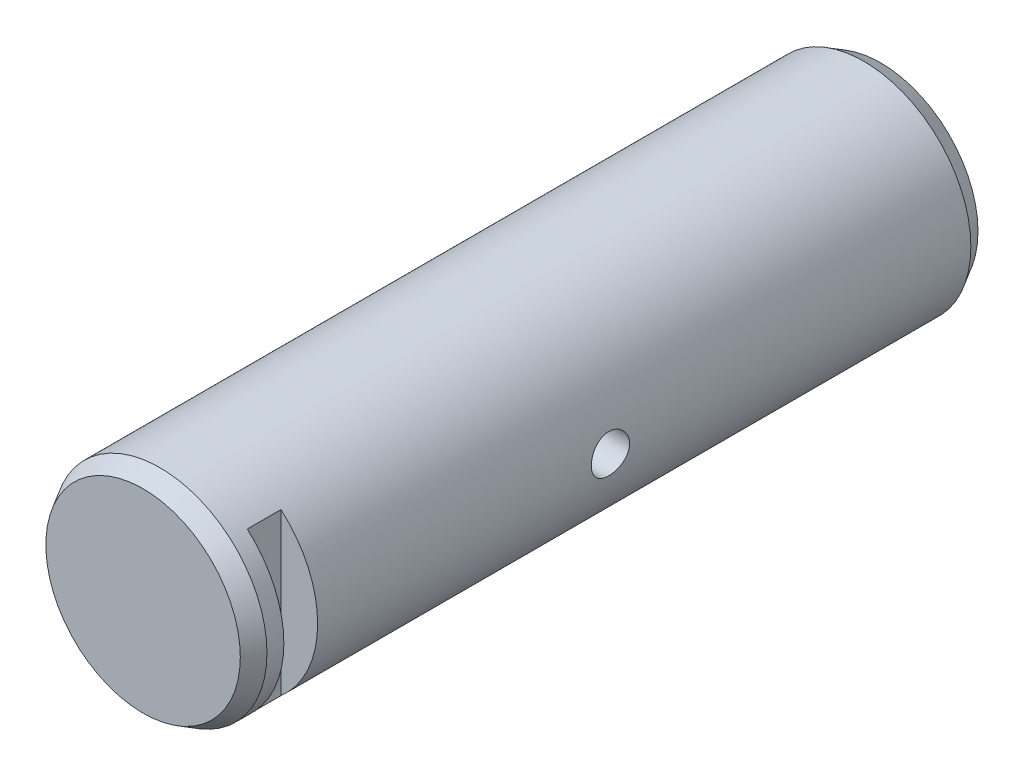
SolidWorks part; units mm, degrees
material "1.7225 (42CrMo4)"
ref_plane "E_Rechts" through (0, 0, 0) normal (0, 0, 1) x (1, 0, 0)
ref_plane "E_Oben" through (0, 0, 0) normal (0, 1, 0) x (1, 0, 0)
ref_plane "E_Vorne" through (0, 0, 0) normal (1, 0, 0) x (0, 0, -1)
ref_axis "E_Drehachse" through (0, 0, 61.5) along (0, 0, -1)
sketch "Skizze1" plane through (0, 0, 0) normal (0, 0, 1) x (1, 0, 0)
  circle A0 centre (0, 0) radius 19
  dimension "D1" = 38
extrude "Aufsatz-Linear austragen1" add sketch "Skizze1" along normal blind 75 and the other way blind 56
sketch "Skizze2" plane through (0, 0, 0) normal (1, 0, 0) x (0, 0, -1)
  line L1 (56, 19) -> (-75, 19) construction
  line L6 (-69, 19) -> (-63, 19)
  line L7 (-69, 19) -> (-69, 13)
  line L8 (-69, 13) -> (-63, 13)
  line L9 (-63, 19) -> (-63, 13)
  line L11 (0, 55) -> (0, -55) construction
  dimension "D1" = 6
  dimension "D2" = 6
  dimension "D3" = 63
hole_wizard "M8 Gewindebohrung1" positions "Skizze3" profile "Skizze4" tap size "M8" standard "DIN"
sketch "Skizze3" plane through (0, 0, -56) normal (0, 0, -1) x (-1, 0, 0)
  point P0 (0, 0)
cosmetic thread "Bohrungsgewinde1" parameters "D1"=16, "D2"=8
sketch "Skizze4" plane through (0, 0, -56) normal (1, 0, 0) x (0, 1, 0)
  line L0 (0, 0) -> (0, 77.0429)
  line L1 (0, 77.0429) -> (3.4, 75)
  line L2 (3.4, 75) -> (3.4, 0)
  line L5 (3.4, 0) -> (0, 0)
  line L10 (0, 77.0429) -> (-3.4, 75) construction
  line L11 (0, -6.35) -> (0, 107.95) construction
  dimension "Bohrerdurchmesser" = 6.8
  dimension "Bohrungstiefe" = 75
  dimension "Spitzenwinkel" = 118
hole_wizard "Kernloch für M8 Gewinde1" positions "Skizze5" profile "Skizze7" hole size "M8" standard "DIN" end condition through all
sketch "Skizze5" plane through (0, 0, 0) normal (1, 0, 0) x (0, 0, -1)
  line L0 (56, -19) -> (56, 19) construction
  point P3 (-11, 0)
  dimension "D1" = 67
sketch "Skizze7" plane through (0, 0, 11) normal (0, 1, 0) x (0, 0, 1)
  line L0 (0, 0) -> (0, 19)
  line L1 (0, 19) -> (3.4, 19)
  line L2 (3.4, 19) -> (3.4, 0)
  line L5 (3.4, 0) -> (0, 0)
  line L11 (0, -6.35) -> (0, 107.95) construction
  dimension "Bohrerdurchmesser" = 6.8
  dimension "Bohrungstiefe" = 19
mirror "Spiegeln1" [suppressed] about plane through (0, 0, 0) normal (1, 0, 0)
sketch "Skizze8" plane through (0, 0, 0) normal (0, 1, 0) x (1, 0, 0)
  line L0 (19, -75) -> (19, -14.4) construction
  line L1 (19, -63) -> (12.5, -63)
  line L2 (19, -63) -> (19, -69)
  line L3 (19, -69) -> (12.5, -69)
  line L4 (12.5, -63) -> (12.5, -69)
  line L5 (-19, -75) -> (19, -75) construction
  dimension "D1" = 12
  dimension "D2" = 6
  dimension "D3" = 6.5
extrude "Schnitt-Linear austragen1" cut sketch "Skizze8" against normal through all both and the other way through all
chamfer "Fase1" distance 3 angle 30 2 edges at (19, 0, -56) (19, 0, 75) first distance on face at (15.75, 0, 66)
